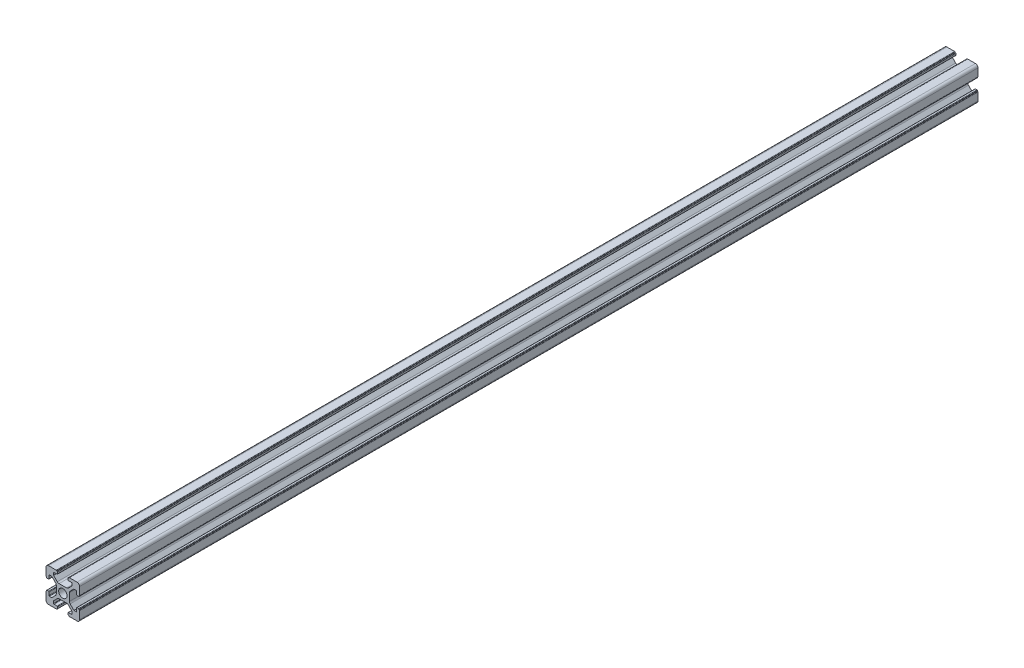
SolidWorks part; units mm, degrees
material "1060 Alloy"
ref_plane "Front Plane" through (0, 0, 0) normal (0, 0, 1) x (1, 0, 0)
ref_plane "Top Plane" through (0, 0, 0) normal (0, 1, 0) x (1, 0, 0)
ref_plane "Right Plane" through (0, 0, 0) normal (1, 0, 0) x (0, 0, -1)
sketch "Sketch1" plane through (0, 0, 0) normal (0, 0, 1) x (1, 0, 0)
  line L0 (3.8995, 3.9005) -> (10.4604, 10.4604) construction
  line L2 (-3.9002, 2.2177) -> (-3.9002, -2.2208)
  line L5 (-3.9005, 3.899) -> (3.9001, -3.8986) construction
  line L6 (-3.9, -3.901) -> (3.8995, 3.9005) construction
  line L7 (-0.0002, 10) -> (-0.0002, -9.9996) construction
  line L8 (-0.0002, -9.9996) -> (-0.0002, 10) construction
  line L9 (5.5006, 6.5619) -> (3.2793, 4.3405)
  line L14 (-10.0002, 9.9996) -> (9.9994, -10) construction
  line L15 (-9.9999, -10.0001) -> (9.9998, 10) construction
  line L16 (6.5613, 5.5012) -> (4.3401, 3.28)
  line L17 (-5.5002, 6.5603) -> (-3.279, 4.3391)
  line L18 (-6.5609, 5.4996) -> (-4.3395, 3.2783)
  line L19 (7.9206, 5.5012) -> (6.5613, 5.5012)
  line L20 (8.2006, 3.3812) -> (8.2006, 5.2212)
  line L21 (9.4206, 3.1012) -> (8.4806, 3.1012)
  line L22 (9.7006, 3.6012) -> (9.7006, 3.3812)
  line L23 (-8.5002, 9.9996) -> (-3.8802, 9.9996)
  line L24 (-3.6002, 9.7196) -> (-3.6002, 9.6996)
  line L25 (-3.6002, 9.6996) -> (-3.3802, 9.6996)
  line L26 (-3.1002, 9.4196) -> (-3.1002, 8.4796)
  line L27 (-3.3802, 8.1996) -> (-5.2202, 8.1996)
  line L28 (-5.5002, 7.9196) -> (-5.5002, 6.5603)
  line L29 (-7.9202, 5.4996) -> (-6.5609, 5.4996)
  line L30 (-8.2002, 3.3796) -> (-8.2002, 5.2196)
  line L31 (-9.4202, 3.0996) -> (-8.4802, 3.0996)
  line L32 (-9.7202, 3.5996) -> (-9.7002, 3.5996)
  line L33 (-9.7002, 3.5996) -> (-9.7002, 3.3796)
  line L34 (-10.0002, 8.4996) -> (-10.0002, 3.8796)
  line L35 (10.0006, 8.5012) -> (10.0006, 3.8812)
  line L36 (8.5006, 10.0012) -> (3.8806, 10.0012)
  line L37 (3.6006, 9.7012) -> (3.3806, 9.7012)
  line L38 (3.1006, 9.4212) -> (3.1006, 8.4812)
  line L39 (3.3806, 8.2012) -> (5.2206, 8.2012)
  line L40 (5.5006, 7.9212) -> (5.5006, 6.5619)
  line L41 (6.5629, -5.4996) -> (4.3415, -3.2783)
  line L42 (5.5022, -6.5603) -> (3.281, -4.3391)
  line L43 (5.5022, -7.9196) -> (5.5022, -6.5603)
  line L44 (3.3822, -8.1996) -> (5.2222, -8.1996)
  line L45 (3.1022, -9.4196) -> (3.1022, -8.4796)
  line L46 (3.6022, -9.6996) -> (3.3822, -9.6996)
  line L47 (8.5022, -9.9996) -> (3.8822, -9.9996)
  line L48 (10.0022, -8.4996) -> (10.0022, -3.8796)
  line L49 (9.7022, -3.5996) -> (9.7022, -3.3796)
  line L50 (9.4222, -3.0996) -> (8.4822, -3.0996)
  line L51 (8.2022, -3.3796) -> (8.2022, -5.2196)
  line L52 (7.9222, -5.4996) -> (6.5629, -5.4996)
  line L53 (-5.4986, -6.5619) -> (-3.2773, -4.3405)
  line L54 (-6.5593, -5.5012) -> (-4.3395, -3.2814)
  line L55 (-7.9186, -5.5012) -> (-6.5593, -5.5012)
  line L56 (-8.1986, -3.3812) -> (-8.1986, -5.2212)
  line L57 (-9.4186, -3.1012) -> (-8.4786, -3.1012)
  line L58 (-9.6986, -3.6012) -> (-9.6986, -3.3812)
  line L59 (-9.9986, -8.5012) -> (-9.9986, -3.8812)
  line L60 (-8.4986, -10.0012) -> (-3.8786, -10.0012)
  line L61 (-3.5986, -9.7012) -> (-3.3786, -9.7012)
  line L62 (-3.0986, -9.4212) -> (-3.0986, -8.4812)
  line L63 (-3.3786, -8.2012) -> (-5.2186, -8.2012)
  line L64 (-5.4986, -7.9212) -> (-5.4986, -6.5619)
  line L65 (-2.233, 3.8998) -> (2.2187, 3.9012)
  line L66 (3.9008, 2.234) -> (3.9022, -2.2177)
  line L67 (2.235, -3.8998) -> (-2.2167, -3.9012)
  line L68 (3.6006, 9.7212) -> (3.6006, 9.6996)
  line L69 (9.7006, 3.6012) -> (9.7206, 3.6012)
  line L70 (-9.6986, -3.6012) -> (-9.7186, -3.6012)
  line L71 (-3.5986, -9.7012) -> (-3.5986, -9.7212)
  line L72 (3.6022, -9.6996) -> (3.6022, -9.7196)
  line L73 (9.7222, -3.5996) -> (9.7022, -3.5996)
  arc A0 (-3.6002, 9.7196) -> (-3.8802, 9.9996) centre (-3.8802, 9.7196) ccw
  arc A1 (-3.3802, 9.6996) -> (-3.1002, 9.4196) centre (-3.3802, 9.4196) cw
  arc A2 (-3.1002, 8.4796) -> (-3.3802, 8.1996) centre (-3.3802, 8.4796) cw
  arc A3 (-10.0002, 8.4996) -> (-8.5002, 9.9996) centre (-8.5002, 8.4996) cw
  arc A4 (-8.2002, 3.3796) -> (-8.4802, 3.0996) centre (-8.4802, 3.3796) cw
  arc A5 (-9.4202, 3.0996) -> (-9.7002, 3.3796) centre (-9.4202, 3.3796) cw
  arc A6 (-9.7202, 3.5996) -> (-10.0002, 3.8796) centre (-9.7202, 3.8796) cw
  arc A7 (-3.279, 4.3391) -> (-2.233, 3.8998) centre (-2.2183, 5.3997) ccw
  arc A8 (-4.3395, 3.2783) -> (-3.9002, 2.2177) centre (-5.4002, 2.2177) cw
  arc A9 (-7.9202, 5.4996) -> (-8.2002, 5.2196) centre (-7.9202, 5.2196) ccw
  arc A10 (-5.2202, 8.1996) -> (-5.5002, 7.9196) centre (-5.2202, 7.9196) ccw
  arc A12 (-4.3395, -3.2814) -> (-3.9002, -2.2208) centre (-5.4002, -2.2208) ccw
  arc A13 (8.2006, 5.2212) -> (7.9206, 5.5012) centre (7.9206, 5.2212) ccw
  arc A14 (8.4806, 3.1012) -> (8.2006, 3.3812) centre (8.4806, 3.3812) cw
  arc A15 (9.7006, 3.3812) -> (9.4206, 3.1012) centre (9.4206, 3.3812) cw
  arc A16 (9.7206, 3.6012) -> (10.0006, 3.8812) centre (9.7206, 3.8812) ccw
  arc A17 (8.5006, 10.0012) -> (10.0006, 8.5012) centre (8.5006, 8.5012) cw
  arc A18 (3.6006, 9.7212) -> (3.8806, 10.0012) centre (3.8806, 9.7212) cw
  arc A19 (3.1006, 9.4212) -> (3.3806, 9.7012) centre (3.3806, 9.4212) cw
  arc A20 (3.3806, 8.2012) -> (3.1006, 8.4812) centre (3.3806, 8.4812) cw
  arc A21 (5.5006, 7.9212) -> (5.2206, 8.2012) centre (5.2206, 7.9212) ccw
  arc A22 (3.2793, 4.3405) -> (2.2187, 3.9012) centre (2.2187, 5.4012) cw
  arc A23 (4.3401, 3.28) -> (3.9008, 2.234) centre (5.4007, 2.2193) ccw
  arc A25 (5.2222, -8.1996) -> (5.5022, -7.9196) centre (5.2222, -7.9196) ccw
  arc A26 (3.1022, -8.4796) -> (3.3822, -8.1996) centre (3.3822, -8.4796) cw
  arc A27 (3.3822, -9.6996) -> (3.1022, -9.4196) centre (3.3822, -9.4196) cw
  arc A28 (3.6022, -9.7196) -> (3.8822, -9.9996) centre (3.8822, -9.7196) ccw
  arc A29 (10.0022, -8.4996) -> (8.5022, -9.9996) centre (8.5022, -8.4996) cw
  arc A30 (9.7222, -3.5996) -> (10.0022, -3.8796) centre (9.7222, -3.8796) cw
  arc A31 (9.4222, -3.0996) -> (9.7022, -3.3796) centre (9.4222, -3.3796) cw
  arc A32 (8.2022, -3.3796) -> (8.4822, -3.0996) centre (8.4822, -3.3796) cw
  arc A33 (7.9222, -5.4996) -> (8.2022, -5.2196) centre (7.9222, -5.2196) ccw
  arc A34 (4.3415, -3.2783) -> (3.9022, -2.2177) centre (5.4022, -2.2177) cw
  arc A35 (3.281, -4.3391) -> (2.235, -3.8998) centre (2.2203, -5.3997) ccw
  circle A36 centre (0.001, -0.001) radius 2.5 construction
  arc A37 (-8.1986, -5.2212) -> (-7.9186, -5.5012) centre (-7.9186, -5.2212) ccw
  arc A38 (-8.4786, -3.1012) -> (-8.1986, -3.3812) centre (-8.4786, -3.3812) cw
  arc A39 (-9.6986, -3.3812) -> (-9.4186, -3.1012) centre (-9.4186, -3.3812) cw
  arc A40 (-9.7186, -3.6012) -> (-9.9986, -3.8812) centre (-9.7186, -3.8812) ccw
  arc A41 (-8.4986, -10.0012) -> (-9.9986, -8.5012) centre (-8.4986, -8.5012) cw
  arc A42 (-3.5986, -9.7212) -> (-3.8786, -10.0012) centre (-3.8786, -9.7212) cw
  arc A43 (-3.0986, -9.4212) -> (-3.3786, -9.7012) centre (-3.3786, -9.4212) cw
  arc A44 (-3.3786, -8.2012) -> (-3.0986, -8.4812) centre (-3.3786, -8.4812) cw
  arc A45 (-5.4986, -7.9212) -> (-5.2186, -8.2012) centre (-5.2186, -7.9212) ccw
  arc A46 (-3.2773, -4.3405) -> (-2.2167, -3.9012) centre (-2.2167, -5.4012) cw
  arc A48 (-4.3381, -3.28) -> (-3.8988, -2.234) centre (-5.3987, -2.2193) ccw [skipped]
  point P0 (0, 0)
  point P9 (-0.0002, 0.0002)
  point P12 (-0.0003, -0.0003)
  point P43 (-3.6002, 9.9996)
  point P46 (-3.1002, 9.6996)
  point P49 (-3.1002, 8.1996)
  point P55 (-8.2002, 3.0996)
  point P58 (-9.7002, 3.0996)
  point P61 (-10.0002, 3.5996)
  point P64 (-2.8395, 3.8996)
  point P67 (-3.9002, 2.839)
  point P70 (-8.2002, 5.4996)
  point P73 (-5.5002, 8.1996)
  point P184 (0.001, 0)
  dimension "D14" = 0.28
  dimension "D15" = 0.28
  dimension "D16" = 0.28
  dimension "D17" = 1.5
  dimension "D18" = 0.28
  dimension "D19" = 1.5
  dimension "D20" = 1.5
  dimension "D21" = 0.28
  dimension "D23" = 5
  dimension "D27" = 1.5
  dimension "D1" = 7.8
  dimension "D2" = 7.8
  dimension "D3" = 3.1
  dimension "D4" = 3.6
  dimension "D5" = 20
  dimension "D6" = 20
  dimension "D7" = 0.75
  dimension "D8" = 1.8
  dimension "D9" = 5.5
  dimension "D10" = 6.4
  dimension "D11" = 6.4
  dimension "D12" = 3.7627
  dimension "D13" = 0.3
  dimension "D24" = 4.62
  dimension "D25" = 3.9005
  dimension "D26" = 7.801
  dimension "D22" = 4
extrude "Boss-Extrude1" add sketch "Sketch1" along normal blind 534.2 contours L53 A46 L67 A35 L42 L43 A25 L44 A26 L45 A27 L46 L72 A28 L47 A29 L48 A30 L73 L49 A31 L50 A32 L51 A33 L52 L41 A34 L66 A23 L16 L19 A13 L20 A14 L21 A15 L22 L69 A16 L35 A17 L36 A18 L68 L37 A19 L38 A20 region at (0.0009, 0, 0)
sketch3d "3DSketch2"
  circle A0 centre (0, 0, 0) radius 2.5
  point P2 (0, 0, 2.5)
extrude "Cut-Extrude1" cut sketch "3DSketch2" along direction (0, 0, 1) on the side of the normal through all contours A0
